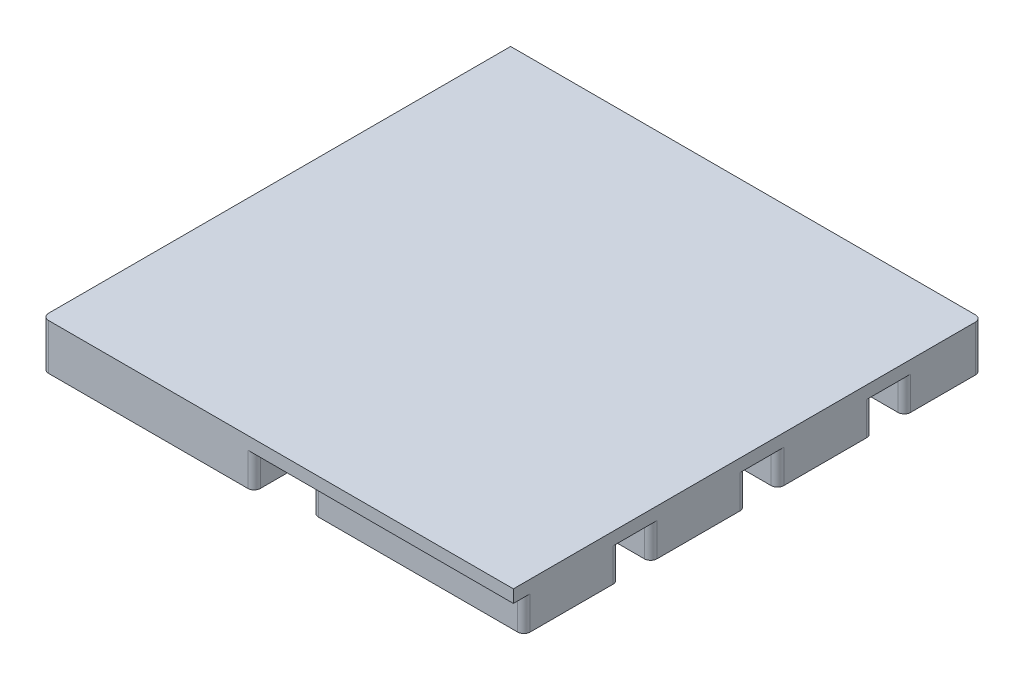
SolidWorks part; units mm, degrees
ref_plane "Front Plane" through (0, 0, 0) normal (0, 0, 1) x (1, 0, 0)
ref_plane "Top Plane" through (0, 0, 0) normal (0, 1, 0) x (1, 0, 0)
ref_plane "Right Plane" through (0, 0, 0) normal (1, 0, 0) x (0, 0, -1)
sketch "Sketch2" plane through (0, 0, 0) normal (0, 1, 0) x (1, 0, 0)
  line L1 (0, 0) -> (149, 0)
  line L2 (0, 0) -> (0, 148.13)
  line L3 (0, 148.13) -> (149, 148.13)
  line L4 (149, 0) -> (149, 148.13)
  dimension "D1" = 149
  dimension "D2" = 148.13
extrude "Boss-Extrude1" add sketch "Sketch2" along normal blind 4
sketch "Sketch3" plane through (0, 4, 0) normal (0, 1, 0) x (1, 0, 0)
  line L0 (0, 148.13) -> (0, 0) construction
  line L1 (149, 148.13) -> (82, 148.13)
  line L2 (149, 148.13) -> (149, 123.63)
  line L3 (149, 123.63) -> (82, 123.63)
  line L4 (82, 148.13) -> (82, 123.63)
  line L5 (0, 144.7967) -> (67, 144.7967)
  line L6 (0, 144.7967) -> (0, 120.2967)
  line L7 (0, 120.2967) -> (67, 120.2967)
  line L8 (67, 144.7967) -> (67, 120.2967)
  line L9 (149, 148.13) -> (0, 148.13) construction
  line L10 (149, 0) -> (149, 148.13) construction
  line L11 (149, 113.73) -> (82, 113.73)
  line L12 (149, 113.73) -> (149, 83.53)
  line L13 (149, 83.53) -> (82, 83.53)
  line L14 (82, 113.73) -> (82, 83.53)
  line L15 (97.3, 113.73) -> (97.3, 99.93) construction
  line L16 (0, 110.3967) -> (67, 110.3967)
  line L17 (0, 110.3967) -> (0, 80.1967)
  line L18 (0, 80.1967) -> (67, 80.1967)
  line L19 (67, 110.3967) -> (67, 80.1967)
  line L20 (149, 73.63) -> (82, 73.63)
  line L21 (149, 73.63) -> (149, 43.43)
  line L22 (149, 43.43) -> (82, 43.43)
  line L23 (82, 73.63) -> (82, 43.43)
  line L24 (0, 70.2967) -> (67, 70.2967)
  line L25 (0, 70.2967) -> (0, 40.0967)
  line L26 (0, 40.0967) -> (67, 40.0967)
  line L27 (67, 70.2967) -> (67, 40.0967)
  line L28 (0, 30.1967) -> (67, 30.1967)
  line L29 (0, 30.1967) -> (0, -0.0033)
  line L30 (0, -0.0033) -> (67, -0.0033)
  line L31 (67, 30.1967) -> (67, -0.0033)
  line L32 (97.3, 99.93) -> (97.3, 95.33) construction
  line L33 (149, 33.53) -> (82, 33.53)
  line L34 (149, 33.53) -> (149, 3.33)
  line L35 (149, 3.33) -> (82, 3.33)
  line L36 (82, 33.53) -> (82, 3.33)
  line L37 (12.85, 144.7967) -> (12.85, 137.9467) construction
  line L38 (12.85, 137.9467) -> (40.15, 137.9467)
  line L39 (12.85, 137.9467) -> (12.85, 133.2967) construction
  line L40 (12.85, 133.2967) -> (12.85, 120.2967) construction
  line L41 (12.85, 133.2967) -> (40.15, 133.2967)
  line L42 (97.3, 148.13) -> (97.3, 140.63) construction
  line L43 (97.3, 140.63) -> (97.3, 135.98) construction
  line L44 (97.3, 135.98) -> (97.3, 123.63) construction
  line L45 (97.3, 140.63) -> (124.6, 140.63)
  line L46 (97.3, 135.98) -> (124.6, 135.98)
  line L47 (0, 0) -> (149, 0) construction
  line L48 (97.3, 95.33) -> (97.3, 83.53) construction
  line L49 (97.3, 99.93) -> (124.6, 99.93)
  line L50 (97.3, 95.33) -> (124.6, 95.33)
  line L51 (12.85, 110.3967) -> (12.85, 96.5967) construction
  line L52 (12.85, 96.5967) -> (12.85, 91.9967) construction
  line L53 (12.85, 91.9967) -> (12.85, 80.1967) construction
  line L54 (12.85, 96.5967) -> (40.15, 96.5967)
  line L55 (12.85, 91.9967) -> (40.15, 91.9967)
  line L56 (12.85, 70.2967) -> (12.85, 56.4967) construction
  line L57 (12.85, 56.4967) -> (12.85, 51.8967) construction
  line L58 (12.85, 51.8967) -> (12.85, 40.0967) construction
  line L59 (12.85, 56.4967) -> (40.15, 56.4967)
  line L60 (12.85, 51.8967) -> (40.15, 51.8967)
  line L61 (97.3, 73.63) -> (97.3, 59.83) construction
  line L62 (97.3, 59.83) -> (97.3, 55.23) construction
  line L63 (97.3, 55.23) -> (97.3, 43.43) construction
  line L64 (97.3, 59.83) -> (124.6, 59.83)
  line L65 (97.3, 55.23) -> (124.6, 55.23)
  line L66 (12.85, 30.1967) -> (12.85, 16.3967) construction
  line L67 (12.85, 16.3967) -> (12.85, 11.7967) construction
  line L68 (12.85, 11.7967) -> (12.85, -0.0033) construction
  line L69 (12.85, 16.3967) -> (40.15, 16.3967)
  line L70 (12.85, 11.7967) -> (40.15, 11.7967)
  line L71 (97.3, 33.53) -> (97.3, 19.73) construction
  line L72 (97.3, 19.73) -> (97.3, 15.13) construction
  line L73 (97.3, 15.13) -> (97.3, 3.33) construction
  line L74 (97.3, 19.73) -> (124.6, 19.73)
  line L75 (97.3, 15.13) -> (124.6, 15.13)
  arc A0 (12.85, 133.2967) -> (12.85, 137.9467) centre (12.85, 135.6217) cw
  arc A2 (40.15, 137.9467) -> (40.15, 133.2967) centre (40.15, 135.6217) cw
  arc A3 (97.3, 135.98) -> (97.3, 140.63) centre (97.3, 138.305) cw
  arc A4 (124.6, 140.63) -> (124.6, 135.98) centre (124.6, 138.305) cw
  arc A5 (97.3, 95.33) -> (97.3, 99.93) centre (97.3, 97.63) cw
  arc A6 (124.6, 99.93) -> (124.6, 95.33) centre (124.6, 97.63) cw
  arc A7 (12.85, 91.9967) -> (12.85, 96.5967) centre (12.85, 94.2967) cw
  arc A9 (40.15, 91.9967) -> (40.15, 96.5967) centre (40.15, 94.2967) ccw
  arc A10 (12.85, 51.8967) -> (12.85, 56.4967) centre (12.85, 54.1967) cw
  arc A11 (40.15, 56.4967) -> (40.15, 51.8967) centre (40.15, 54.1967) cw
  arc A12 (97.3, 55.23) -> (97.3, 59.83) centre (97.3, 57.53) cw
  arc A13 (124.6, 59.83) -> (124.6, 55.23) centre (124.6, 57.53) cw
  arc A14 (12.85, 11.7967) -> (12.85, 16.3967) centre (12.85, 14.0967) cw
  arc A15 (40.15, 16.3967) -> (40.15, 11.7967) centre (40.15, 14.0967) cw
  arc A16 (97.3, 15.13) -> (97.3, 19.73) centre (97.3, 17.43) cw
  arc A17 (124.6, 19.73) -> (124.6, 15.13) centre (124.6, 17.43) cw
  line M24 (0, 148.13) -> (0, 0)
  line M25 (0, 0) -> (149, 0)
  line M26 (149, 0) -> (149, 148.13)
  line M27 (149, 148.13) -> (0, 148.13)
  dimension "D31" = 24.4
  dimension "D1" = 67
  dimension "D2" = 24.5
  dimension "D3" = 3.3333
  dimension "D4" = 67
  dimension "D5" = 24.5
  dimension "D6" = 9.9
  dimension "D7" = 30.2
  dimension "D8" = 67
  dimension "D9" = 30.2
  dimension "D10" = 9.9
  dimension "D11" = 67
  dimension "D12" = 9.9
  dimension "D13" = 30.2
  dimension "D14" = 67
  dimension "D15" = 9.9
  dimension "D16" = 30.2
  dimension "D17" = 67
  dimension "D18" = 30.2
  dimension "D19" = 9.9
  dimension "D20" = 67
  dimension "D21" = 9.9
  dimension "D22" = 30.2
  dimension "D23" = 67
  dimension "D24" = 6.85
  dimension "D25" = 4.65
  dimension "D26" = 27.3
  dimension "D27" = 12.85
  dimension "D28" = 7.5
  dimension "D29" = 4.65
  dimension "D30" = 27.3
  dimension "D32" = 13.8
  dimension "D33" = 11.8
  dimension "D34" = 27.3
  dimension "D35" = 13.8
  dimension "D36" = 11.8
  dimension "D37" = 27.3
  dimension "D38" = 13.8
  dimension "D39" = 11.8
  dimension "D40" = 13.8
  dimension "D41" = 11.8
  dimension "D42" = 13.8
  dimension "D43" = 11.8
  dimension "D44" = 13.8
  dimension "D45" = 11.8
extrude "Boss-Extrude3" add sketch "Sketch3" against normal blind 14.5 contours L8 L5 L7 L38 A2 L41 A0 M24 | L4 L3 L45 A4 L46 A3 M27 M26 | L19 L16 L18 A9 L55 A7 L54 M24 | L11 L14 L13 L49 A6 L50 A5 M26 | L27 L24 L26 L59 A11 L60 A10 M24 | L20 L23 L22 L64 A13 L65 A12 M26 | L31 L28 L69 A15 L70 A14 M24 M25 | L33 L36 L35 L74 A17 L75 A16 M26 region at (115.9373, 4, -135.6469) region at (148.2651, 4, -98.63) region at (34.1727, 4, -132.2512) region at (148.2651, 4, -58.53) region at (33.5, 4, -109.6618) region at (148.2651, 4, -18.43) region at (33.5, 4, -69.5618) region at (33.5, 4, -29.4618)
fillet "Fillet1" radius 2 32 edges at (149, -5.25, -3.33) (149, -5.25, -33.53) (82, -5.25, -33.53) (82, -5.25, -3.33) (67, -5.25, 0) (0, -3.25, 0) (0, -5.25, -30.1967) (67, -5.25, -30.1967) (67, -5.25, -40.0967) (0, -5.25, -40.0967) (149, -5.25, -43.43) (82, -5.25, -43.43) (82, -5.25, -73.63) (67, -5.25, -70.2967) (0, -5.25, -70.2967) (0, -5.25, -80.1967) (82, -5.25, -83.53) (67, -5.25, -80.1967) (0, -5.25, -110.3967) (149, -5.25, -83.53) (149, -5.25, -73.63) (149, -5.25, -113.73) (67, -5.25, -110.3967) (82, -5.25, -113.73) (0, -5.25, -120.2967) (67, -5.25, -120.2967) (67, -5.25, -144.7967) (0, -5.25, -144.7967) (82, -5.25, -123.63) (149, -5.25, -123.63) (149, -3.25, -148.13) (82, -5.25, -148.13)
